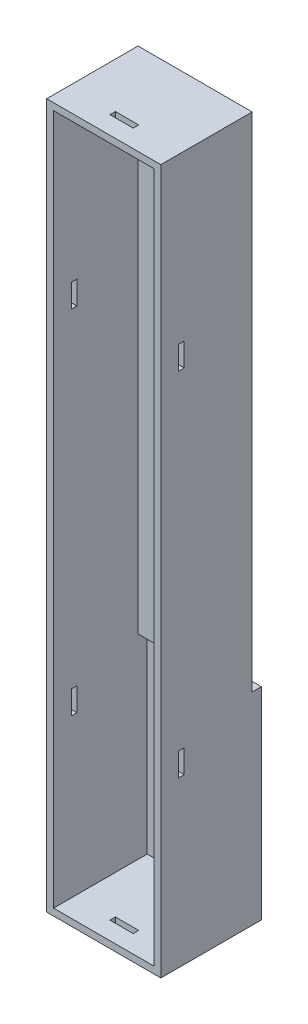
SolidWorks part; units mm, degrees
ref_plane "Front Plane" through (0, 0, 0) normal (1, 0, 0) x (0, 1, 0)
ref_plane "Top Plane" through (0, 0, 0) normal (0, 0, 1) x (0, 1, 0)
ref_plane "Right Plane" through (0, 0, 0) normal (0, 1, 0) x (-1, 0, 0)
sketch "Sketch2" plane through (0, 0, 0) normal (0, 0, 1) x (0, 1, 0)
  line L0 (0, 12.5) -> (154.25, 12.5) construction
  line L1 (0, 0) -> (154.25, 0)
  line L2 (0, 0) -> (0, 25)
  line L3 (0, 25) -> (154.25, 25)
  line L4 (154.25, 0) -> (154.25, 25)
  line L5 (5.5, 6.625) -> (35.75, 6.625)
  line L6 (5.5, 6.625) -> (5.5, 18.375)
  line L7 (5.5, 18.375) -> (35.75, 18.375)
  line L8 (35.75, 6.625) -> (35.75, 18.375)
  line L9 (5.5, 6.625) -> (35.75, 18.375) construction
  line L10 (5.5, 18.375) -> (35.75, 6.625) construction
  line L12 (69.25, 0) -> (99.25, 0)
  line L13 (69.25, 0) -> (69.25, 25)
  line L14 (69.25, 25) -> (99.25, 25)
  line L15 (99.25, 0) -> (99.25, 25)
  line L16 (69.25, 0) -> (99.25, 25) construction
  line L17 (69.25, 25) -> (99.25, 0) construction
  line L18 (99.25, 0) -> (129.25, 0)
  line L19 (99.25, 0) -> (99.25, 25)
  line L20 (99.25, 25) -> (129.25, 25)
  line L21 (129.25, 0) -> (129.25, 25)
  line L22 (99.25, 0) -> (129.25, 25) construction
  line L23 (99.25, 25) -> (129.25, 0) construction
  line L24 (44.25, 0) -> (69.25, 0)
  line L25 (44.25, 0) -> (44.25, 25)
  line L26 (44.25, 25) -> (69.25, 25)
  line L27 (69.25, 0) -> (69.25, 25)
  line L28 (44.25, 0) -> (69.25, 25) construction
  line L29 (44.25, 25) -> (69.25, 0) construction
  line L30 (129.25, 0) -> (154.25, 0)
  line L31 (129.25, 0) -> (129.25, 25)
  line L32 (129.25, 25) -> (154.25, 25)
  line L33 (154.25, 0) -> (154.25, 25)
  line L34 (129.25, 0) -> (154.25, 25) construction
  line L35 (129.25, 25) -> (154.25, 0) construction
  point P5 (20.625, 12.5)
  point P10 (114.25, 12.5)
  point P15 (84.25, 12.5)
  point P22 (141.75, 12.5)
  point P24 (56.75, 12.5)
  dimension "D1" = 30.25
  dimension "D2" = 11.75
  dimension "D3" = 5.5
  dimension "D5" = 25
  dimension "D6" = 25
  dimension "D4" = 25
  dimension "D7" = 8.5
  dimension "D8" = 30
  dimension "D9" = 110
extrude "Boss-Extrude1" add sketch "Sketch2" along normal blind 1.5 contours L1 L25 L3 L2 L8 L5 L6 L7 region at (-12.5, 0.5082, 0)
sketch "Sketch3" plane through (0, 44.25, 0) normal (0, 1, 0) x (-1, 0, 0)
  line L0 (25, 1.5) -> (25, 0) construction
  line L2 (0, 1.5) -> (0, 3.5)
  line L3 (0, 3.5) -> (25, 3.5)
  line L4 (25, 1.5) -> (25, 3.5)
  line L5 (0, 1.5) -> (0, 0) construction
  line L11 (25, 1.5) -> (0, 1.5)
  line L12 (0, 1.5) -> (25, 1.5) construction
  line L13 (0, 1.5) -> (25, 1.5) construction
  point P0 (25, 0.2958)
  point P7 (0.2703, 1.5988)
  point P8 (0, 1.5747)
  point P11 (-0.5496, 1.5)
  point P12 (0, 1.5)
  point P16 (0, 1.5)
  dimension "D1" = 2
extrude "Boss-Extrude2" add sketch "Sketch3" along normal blind 110 separate body
sketch "Sketch4" plane through (0, 0, 0) normal (1, 0, 0) x (0, 1, 0)
  line L0 (44.25, 3.5) -> (44.25, 1.5) construction
  line L1 (44.25, 3.5) -> (44.25, 1.5)
  line L2 (44.25, 1.5) -> (42.25, 1.5)
  line L3 (0, 1.5) -> (44.25, 1.5) construction
  line L4 (42.25, 1.5) -> (44.25, 3.5)
extrude "Boss-Extrude3" add sketch "Sketch4" against normal up to surface (25 mm away) up to face at (-25, 99.25, 2.5)
sketch "Sketch5" plane through (0, 0, 1.5) normal (0, 0, 1) x (1, 0, 0)
  line L6 (0, 0) -> (0, 42.25) construction
  line L7 (0, 0) -> (-25, 0) construction
  line L8 (-25, 0) -> (-25, 42.25) construction
  line L9 (-1.5, 42.25) -> (-1.5, 1.5)
  line L10 (-1.5, 1.5) -> (-23.5, 1.5)
  line L11 (-23.5, 1.5) -> (-23.5, 42.25)
  line L12 (-1.5, 42.25) -> (-1.5, 1.5)
  line L13 (-1.5, 1.5) -> (-23.5, 1.5)
  line L14 (-23.5, 1.5) -> (-23.5, 42.25)
  line L15 (0, 0) -> (0, 42.25)
  line L16 (0, 0) -> (-25, 0)
  line L17 (-25, 0) -> (-25, 42.25)
  line L18 (0, 42.25) -> (-1.5, 42.25)
  line L19 (-23.5, 42.25) -> (-25, 42.25)
  dimension "D1" = 1.5
extrude "Boss-Extrude4" add sketch "Sketch5" along normal blind 7.3
sketch "Sketch6" plane through (0, 42.25, 0) normal (0, 1, 0) x (-1, 0, 0)
  line L4 (23.5, 1.5) -> (25, 1.5)
  line L5 (25, 1.5) -> (25, 8.8)
  line L6 (25, 8.8) -> (23.5, 8.8)
  line L7 (23.5, 8.8) -> (23.5, 1.5)
  line L9 (25, 1.5) -> (25, 8.8)
  line L10 (25, 8.8) -> (23.5, 8.8)
  line L11 (23.5, 8.8) -> (23.5, 1.5)
  line L12 (0, 1.5) -> (1.5, 1.5)
  line L13 (1.5, 1.5) -> (1.5, 8.8)
  line L14 (1.5, 8.8) -> (0, 8.8)
  line L15 (0, 8.8) -> (0, 1.5)
  line L17 (1.5, 1.5) -> (1.5, 8.8)
  line L18 (1.5, 8.8) -> (0, 8.8)
  line L19 (0, 8.8) -> (0, 1.5)
  line L23 (23.5, 1.5) -> (25, 1.5)
  line L25 (0, 1.5) -> (1.5, 1.5)
  line M9 (23.5, 1.5) -> (25, 1.5)
  line M10 (25, 1.5) -> (25, 8.8)
  line M11 (25, 8.8) -> (23.5, 8.8)
  line M12 (23.5, 8.8) -> (23.5, 1.5)
  dimension "D1" = 0
  dimension "D2" = 0
extrude "Boss-Extrude5" add sketch "Sketch6" along normal up to surface (112 mm away) contours M12 M9 M10 M11 | L17 L18 L19 L25 region at (-24.25, 42.25, 5.15) up to face at (-12.5, 154.25, 2.5)
sketch "Sketch8" plane through (-23.5, 0, 0) normal (1, 0, 0) x (0, 1, 0)
  line L0 (1.5, 8.8) -> (154.25, 8.8) construction
  line L1 (154.25, 3.5) -> (152.75, 3.5)
  line L2 (154.25, 3.5) -> (154.25, 8.8)
  line L3 (154.25, 8.8) -> (152.75, 8.8)
  line L4 (152.75, 3.5) -> (152.75, 8.8)
  dimension "D1" = 1.5
extrude "Boss-Extrude6" add sketch "Sketch8" along normal up to surface (22 mm away) up to face at (-1.5, 66.3333, 4.6)
sketch "Sketch9" plane through (0, 0, 1.5) normal (0, 0, -1) x (1, 0, 0)
  line L1 (-25, -44.25) -> (0, -44.25) construction
  line L2 (-25, -44.25) -> (-25, -69.25) construction
  line L3 (-25, -69.25) -> (0, -69.25) construction
  line L4 (0, -44.25) -> (0, -69.25) construction
  line L5 (-25, -44.25) -> (0, -69.25) construction
  line L6 (-25, -69.25) -> (0, -44.25) construction
  line L10 (-25, -69.25) -> (0, -69.25) construction
  line L11 (-25, -69.25) -> (-25, -99.25) construction
  line L12 (-25, -99.25) -> (0, -99.25) construction
  line L13 (0, -69.25) -> (0, -99.25) construction
  line L14 (-25, -69.25) -> (0, -99.25) construction
  line L15 (-25, -99.25) -> (0, -69.25) construction
  line L16 (-25, -99.25) -> (0, -99.25) construction
  line L17 (-25, -99.25) -> (-25, -129.25) construction
  line L18 (-25, -129.25) -> (0, -129.25) construction
  line L19 (0, -99.25) -> (0, -129.25) construction
  line L20 (-25, -99.25) -> (0, -129.25) construction
  line L21 (-25, -129.25) -> (0, -99.25) construction
  line L22 (-25, -129.25) -> (0, -129.25) construction
  line L23 (-25, -129.25) -> (-25, -154.25) construction
  line L24 (-25, -154.25) -> (0, -154.25) construction
  line L25 (0, -129.25) -> (0, -154.25) construction
  line L26 (-25, -129.25) -> (0, -154.25) construction
  line L27 (-25, -154.25) -> (0, -129.25) construction
  line L28 (-23.5, -44.25) -> (-1.5, -44.25) construction
  line L29 (-15.6, -53.65) -> (-9.4, -53.65)
  line L30 (-15.6, -53.65) -> (-15.6, -59.85)
  line L31 (-15.6, -59.85) -> (-9.4, -59.85)
  line L32 (-9.4, -53.65) -> (-9.4, -59.85)
  line L33 (-15.6, -53.65) -> (-9.4, -59.85) construction
  line L34 (-15.6, -59.85) -> (-9.4, -53.65) construction
  line L35 (-15.6, -81.15) -> (-9.4, -81.15)
  line L36 (-15.6, -81.15) -> (-15.6, -87.35)
  line L37 (-15.6, -87.35) -> (-9.4, -87.35)
  line L38 (-9.4, -81.15) -> (-9.4, -87.35)
  line L39 (-15.6, -81.15) -> (-9.4, -87.35) construction
  line L40 (-15.6, -87.35) -> (-9.4, -81.15) construction
  line L41 (-15.6, -111.15) -> (-9.4, -111.15)
  line L42 (-15.6, -111.15) -> (-15.6, -117.35)
  line L43 (-15.6, -117.35) -> (-9.4, -117.35)
  line L44 (-9.4, -111.15) -> (-9.4, -117.35)
  line L45 (-15.6, -111.15) -> (-9.4, -117.35) construction
  line L46 (-15.6, -117.35) -> (-9.4, -111.15) construction
  line L47 (-15.6, -138.65) -> (-9.4, -138.65)
  line L48 (-15.6, -138.65) -> (-15.6, -144.85)
  line L49 (-15.6, -144.85) -> (-9.4, -144.85)
  line L50 (-9.4, -138.65) -> (-9.4, -144.85)
  line L51 (-15.6, -138.65) -> (-9.4, -144.85) construction
  line L52 (-15.6, -144.85) -> (-9.4, -138.65) construction
  line L53 (-25, -154.25) -> (-25, -44.25) construction
  line L54 (0, -154.25) -> (0, -44.25) construction
  line L55 (0, -154.25) -> (-25, -154.25) construction
  point P0 (-12.5, -56.75)
  point P1 (-22.9871, -67.2371)
  point P5 (-12.5, -114.25)
  point P12 (-12.5, -84.25)
  point P13 (0, 0)
  point P21 (-12.5, -141.75)
  point P26 (-12.5, -84.25)
  point P31 (-12.5, -56.75)
  point P38 (-12.5, -114.25)
  point P43 (-12.5, -141.75)
  point P50 (0, 0)
  dimension "D1" = 30
  dimension "D2" = 6.2
extrude "Cut-Extrude1" cut sketch "Sketch9" against normal up to surface (2 mm away) contours L50 L47 L48 L49 | L44 L41 L42 L43 | L32 L31 L30 L29 | L38 L37 L36 L35 region at (-12.5, 114.25, 1.5) region at (-12.5, 141.75, 1.5) up to face at (-12.5, 98.5, 3.5)
sketch "Sketch10" plane through (0, 0, 1.5) normal (0, 0, -1) x (1, 0, 0)
  line L14 (0, -44.25) -> (-25, -44.25)
  line L15 (-25, -44.25) -> (-25, -154.25)
  line L16 (-25, -154.25) -> (0, -154.25)
  line L17 (0, -154.25) -> (0, -44.25)
  line L18 (0, -44.25) -> (-25, -44.25)
  line L19 (-25, -44.25) -> (-25, -154.25)
  line L20 (-25, -154.25) -> (0, -154.25)
  line L21 (0, -154.25) -> (0, -44.25)
  dimension "D1" = 0
extrude "Cut-Extrude2" cut sketch "Sketch10" against normal blind 0.5
sketch "Sketch11" plane through (0, 0, 8.8) normal (0, 0, 1) x (1, 0, 0)
  line L0 (-1.5, 1.5) -> (-23.5, 1.5) construction
  line L1 (-23.5, 1.5) -> (-23.5, 152.75) construction
  line L2 (-1.5, 152.75) -> (-1.5, 1.5) construction
  line L3 (-1.5, 152.75) -> (-23.5, 152.75) construction
  line L4 (-25, 0) -> (0, 0)
  line L5 (0, 0) -> (0, 154.25)
  line L6 (0, 154.25) -> (-25, 154.25)
  line L7 (-25, 154.25) -> (-25, 0)
  line L8 (-25, 0) -> (0, 0)
  line L9 (0, 0) -> (0, 154.25)
  line L11 (-25, 154.25) -> (-25, 0)
  line L12 (-1.5, 1.5) -> (-23.5, 1.5)
  line L13 (-23.5, 1.5) -> (-23.5, 152.75)
  line L14 (-1.5, 152.75) -> (-1.5, 1.5)
  line L15 (-1.5, 152.75) -> (-23.5, 152.75)
  line L23 (0, 154.25) -> (-25, 154.25)
  dimension "D1" = 0
extrude "Boss-Extrude7" add sketch "Sketch11" along normal blind 13.2
sketch "Sketch12" plane through (0, 0, 0) normal (0, -1, 0) x (1, 0, 0)
  line L0 (-12.5, 22) -> (-12.5, -1.5845) construction
  line L1 (-25, 22) -> (0, 22) construction
  line L3 (-15.05, 18.1) -> (-9.95, 18.1)
  line L4 (-15.05, 18.1) -> (-15.05, 16.9)
  line L5 (-15.05, 16.9) -> (-9.95, 16.9)
  line L6 (-9.95, 18.1) -> (-9.95, 16.9)
  line L7 (-15.05, 18.1) -> (-9.95, 16.9) construction
  line L8 (-15.05, 16.9) -> (-9.95, 18.1) construction
  point P5 (-12.5, 17.5)
  dimension "D1" = 3.9
  dimension "D3" = 5.1
extrude "Cut-Extrude3" cut sketch "Sketch12" against normal through all
sketch "Sketch13" plane through (0, 0, 0) normal (1, 0, 0) x (0, 1, 0)
  line L0 (77.125, 22) -> (77.125, -6.2793) construction
  line L1 (0, 22) -> (154.25, 22) construction
  line L2 (0, 22) -> (77.125, 22) construction
  line L3 (38.5625, 22) -> (38.5625, -9.2645) construction
  line L5 (36.0125, 16.9) -> (41.1125, 16.9)
  line L6 (36.0125, 16.9) -> (36.0125, 18.1)
  line L7 (36.0125, 18.1) -> (41.1125, 18.1)
  line L8 (41.1125, 16.9) -> (41.1125, 18.1)
  line L9 (36.0125, 16.9) -> (41.1125, 18.1) construction
  line L10 (36.0125, 18.1) -> (41.1125, 16.9) construction
  point P8 (38.5625, 17.5)
  dimension "D1" = 3.9
  dimension "D3" = 5.1
extrude "Cut-Extrude4" cut sketch "Sketch13" against normal through all
ref_plane "Plane1" through (0, 77.125, 0) normal (0, -1, 0) x (-1, 0, 0)
mirror "Mirror1" about plane through (0, 77.125, 0) normal (0, -1, 0) of "Cut-Extrude4"
equation "\"SSD1306_screen_w\" = 11.5mm"
equation "\"SSD1306_screen_l\" = 30mm"
equation "\"SSD1306_screen_marge\" = 0.25mm"
equation "\"D1@Sketch2\"=\"SSD1306_screen_l\"+\"SSD1306_screen_marge\""
equation "\"D2@Sketch2\"=\"SSD1306_screen_w\"+\"SSD1306_screen_marge\""
equation "\"SSD1306_screen_t\" = 1.5mm"
equation "\"D1@Boss-Extrude1\"=\"SSD1306_screen_t\""
equation "\"Button_plate_l\"= \"D9@Sketch2\""
equation "\"D1@Boss-Extrude2\"=\"Button_plate_l\""
equation "\"SSD1306_PCB_Screen_H\" = 7.3mm"
equation "\"D1@Boss-Extrude4\"=\"SSD1306_PCB_Screen_H\""
equation "\"clip_h\" = 5mm"
equation "\"clip_l\" = 5mm"
equation "\"clip_w\" = 1.5mm"
equation "\"clip_lip_h\" = 1mm"
equation "\"clip_lip_l\" = 0.5mm"
equation "\"D1@Sketch12\"=\"clip_h\" - \"clip_lip_h\" -0.1"
equation "\"D2@Sketch12\"=\"clip_lip_h\"+0.2"
equation "\"D3@Sketch12\"=\"clip_l\"+0.1"
equation "\"D1@Sketch13\"=\"clip_h\"-\"clip_lip_h\"-0.1"
equation "\"D2@Sketch13\"=\"clip_lip_h\"+0.2"
equation "\"D3@Sketch13\"=\"clip_l\"+0.1"
equation "\"D1@Boss-Extrude7\"= 3.20 + 10"
